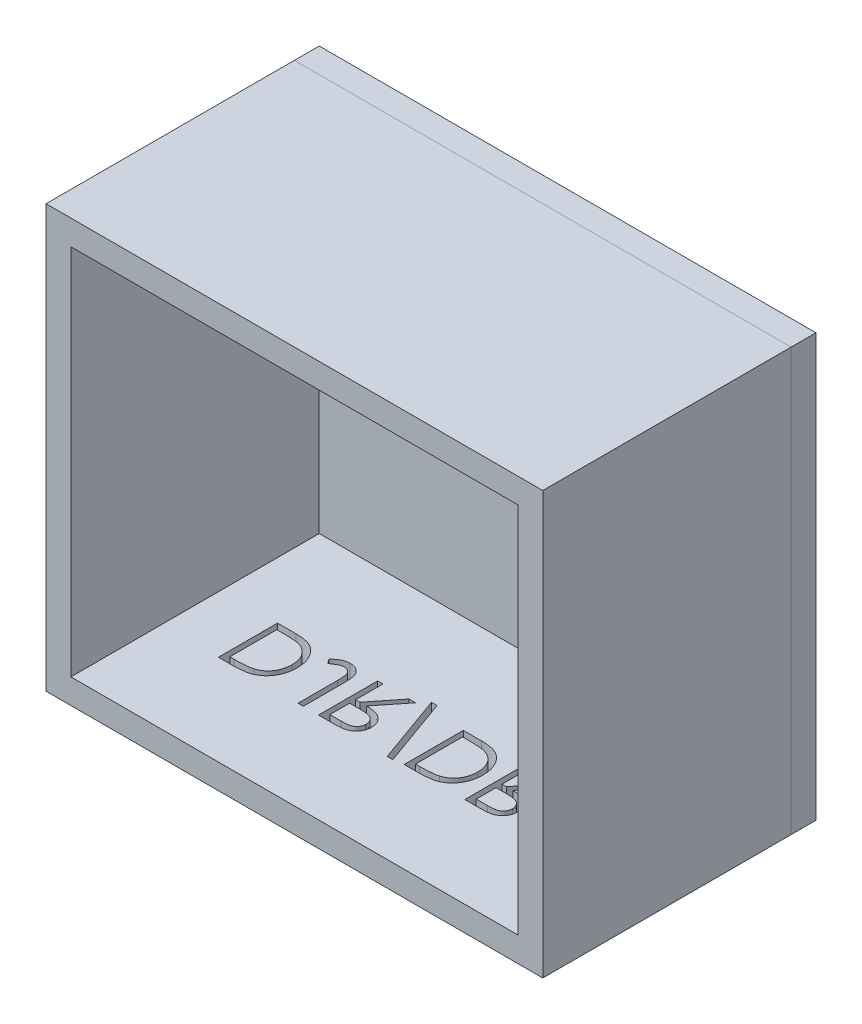
SolidWorks part; units mm, degrees
ref_plane "Alzado" through (0, 0, 0) normal (0, 0, 1) x (1, 0, 0)
ref_plane "Planta" through (0, 0, 0) normal (0, 1, 0) x (1, 0, 0)
ref_plane "Vista lateral" through (0, 0, 0) normal (1, 0, 0) x (0, 0, -1)
sketch "Croquis1" plane through (0, 0, 0) normal (0, 0, 1) x (1, 0, 0)
  line L1 (-100, 85) -> (100, 85)
  line L2 (-100, 85) -> (-100, -85)
  line L3 (-100, -85) -> (100, -85)
  line L4 (100, 85) -> (100, -85)
  line L5 (-100, 85) -> (100, -85) construction
  line L6 (-100, -85) -> (100, 85) construction
  line L7 (-90, 75) -> (90, 75)
  line L8 (-90, 75) -> (-90, -75)
  line L9 (-90, -75) -> (90, -75)
  line L10 (90, 75) -> (90, -75)
  line L11 (-90, 75) -> (90, -75) construction
  line L12 (-90, -75) -> (90, 75) construction
  point P0 (0, 0)
  point P5 (0, 0)
  dimension "D1" = 200
  dimension "D2" = 170
  dimension "D3" = 10
  dimension "D4" = 10
extrude "Saliente-Extruir1" add sketch "Croquis1" along normal blind 10 contours L10 L7 L8 L9 | L4 L1 L2 L3 L7 L10 L9 L8 region at (0, 82.3751, 0) region at (0, 0, 0)
extrude "Saliente-Extruir2" add sketch "Croquis1<3>" along normal blind 100 from surface separate body starting at face at (0, 0, 10)
sketch "Croquis1<3>" plane through (0, 0, 0) normal (0, 0, 1) x (1, 0, 0) same geometry as "Croquis1"
sketch "Croquis3" plane through (0, -85, 0) normal (0, -1, 0) x (1, 0, 0)
  text T0 "DJR/DRJ" font "Century Gothic" height in points 90
extrude "Cortar-Extruir3" cut sketch "Croquis3" against normal blind 100
